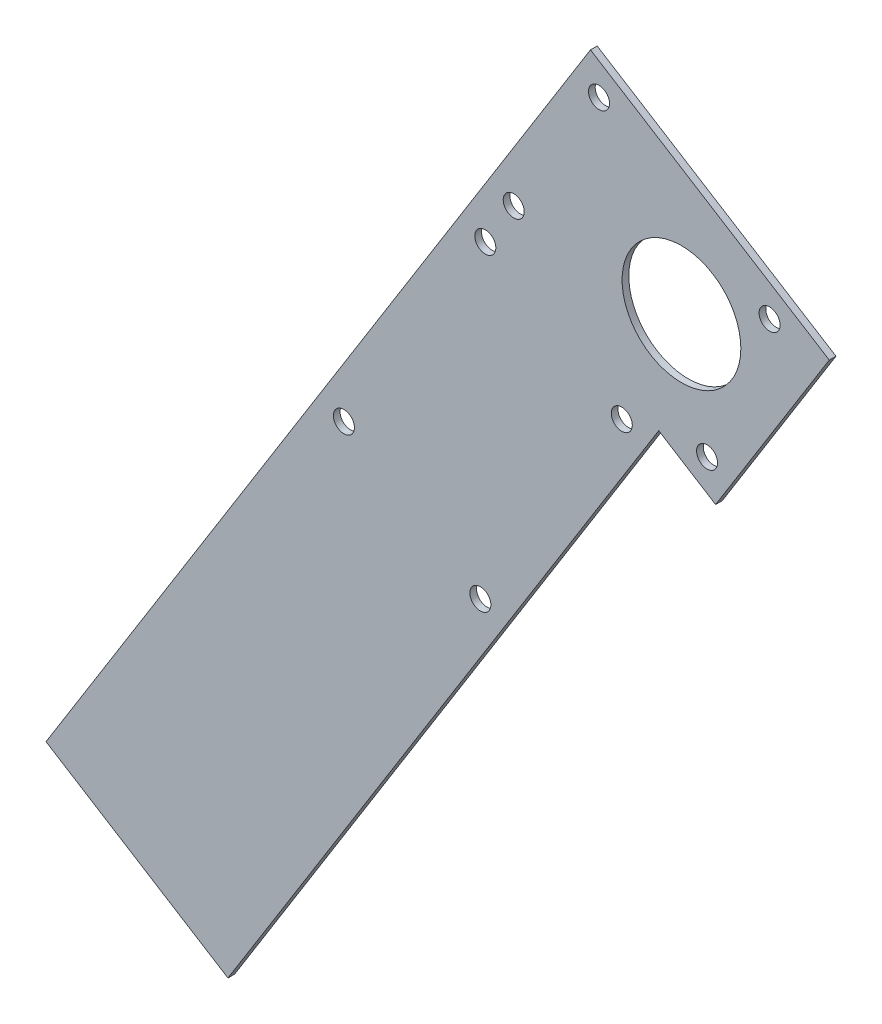
SolidWorks part; units mm, degrees
ref_plane "Front Plane" through (0, 0, 0) normal (0, 0, 1) x (1, 0, 0)
ref_plane "Top Plane" through (0, 0, 0) normal (0, 1, 0) x (1, 0, 0)
ref_plane "Right Plane" through (0, 0, 0) normal (1, 0, 0) x (0, 0, -1)
sketch "Sketch2" plane through (0, 0, 375.412) normal (0, 0, -1) x (-1, 0, 0)
  line L1 (-54.5235, -26.5823) -> (-27.6036, -69.6631)
  line L2 (-27.6036, -69.6631) -> (-14.1408, -61.2506)
  line L3 (-14.1408, -61.2506) -> (87.8513, -224.4722)
  line L4 (-14.1408, -61.2506) -> (154.1085, -330.5059) construction
  line L5 (87.8513, -224.4722) -> (130.9322, -197.5523)
  line L6 (28.94, -34.3308) -> (197.1894, -303.586) construction
  line L7 (130.9322, -197.5523) -> (2.0201, 8.7501)
  line L8 (112.4148, 77.7323) -> (-54.5235, -26.5823) construction
  line L9 (2.0201, 8.7501) -> (-54.5235, -26.5823)
extrude "Boss-Extrude1" add sketch "Sketch2" along normal blind 1.5875
hole_wizard "#10 Clearance Hole1" positions "Sketch3" profile "Sketch4" hole size "#10" standard "ANSI Inch" end condition through all
sketch "Sketch3" plane through (0, 0, 373.8245) normal (0, 0, -1) x (-1, 0, 0)
  point P0 (-5.3907, -63.2708)
  point P3 (-25.5835, -60.913)
  point P6 (-40.3883, -25.2374)
  point P9 (0, 0)
  point P12 (20.1899, -32.3106)
  point P15 (26.9199, -43.0808)
  point P18 (60.4039, -96.6664)
  point P21 (28.0932, -116.8563)
sketch "Sketch4" plane through (5.3907, -63.2708, 373.8245) normal (1, 0, 0) x (0, 1, 0)
  line L0 (0, 0) -> (0, 1.5875)
  line L1 (0, 1.5875) -> (2.4892, 1.5875)
  line L2 (2.4892, 1.5875) -> (2.4892, 0)
  line L5 (2.4892, 0) -> (0, 0)
  line L11 (0, -6.35) -> (0, 107.95) construction
  dimension "Thru Hole Dia." = 4.9784
  dimension "Thru Hole Depth" = 1.5875
sketch "Sketch5" plane through (0, 0, 375.412) normal (0, 0, 1) x (1, 0, 0)
  circle A0 centre (19.5231, -34.6627) radius 14.0572
extrude "Cut-Extrude1" cut sketch "Sketch5" against normal blind 2.54
